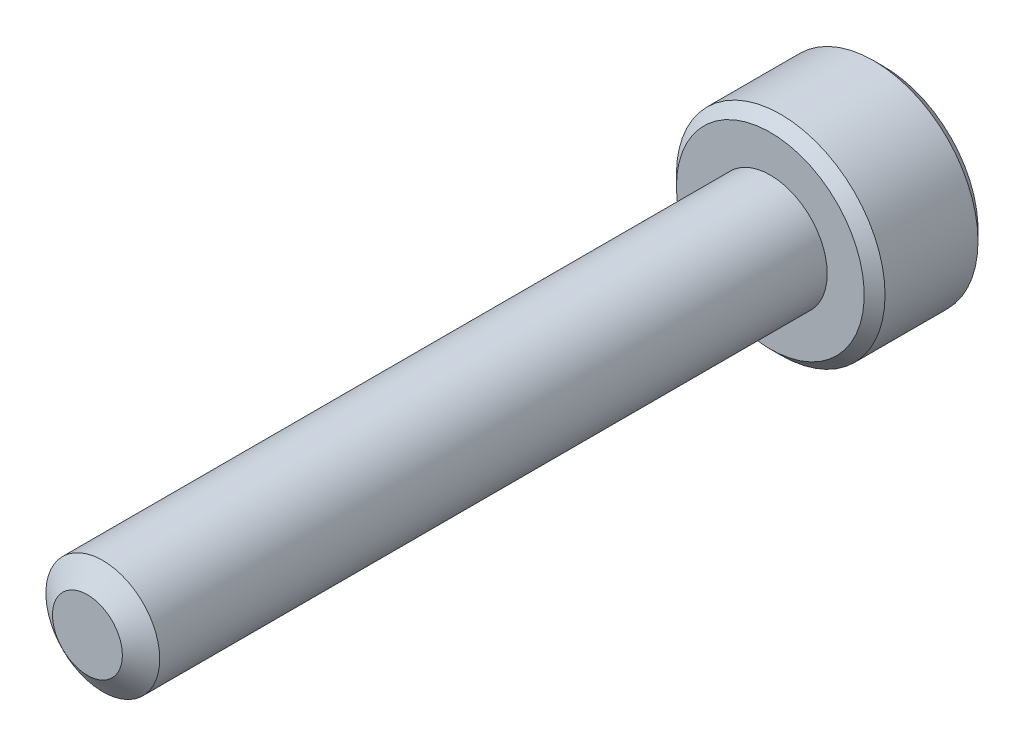
SolidWorks part; units mm, degrees
other "DetailItem1"
material "1.4310 (X10CrNi18-8)"
ref_plane "Front Plane" through (0, 0, 0) normal (0, 0, 1) x (1, 0, 0)
ref_plane "Top Plane" through (0, 0, 0) normal (0, 1, 0) x (1, 0, 0)
ref_plane "Right Plane" through (0, 0, 0) normal (1, 0, 0) x (0, 0, -1)
sketch "Sketch1" plane through (0, 0, 0) normal (0, 0, 1) x (1, 0, 0)
  circle A0 centre (0, 0) radius 1.5
  dimension "OD" = 3
extrude "Extrude1" add sketch "Sketch1" against normal blind 18
sketch "Sketch2" plane through (0, 0, 0) normal (0, 0, 1) x (1, 0, 0)
  circle A0 centre (0, 0) radius 1.5 construction
  circle A1 centre (0, 0) radius 1.5
curve "Helix/Spiral1" pitch 0.5 height 18.5 turns 37 parameters "pitch"=0.5
sketch "Sketch3" plane through (0, 0, 0) normal (1, 0, 0) x (0, 0, -1)
  line L0 (-0.4375, 1.5) -> (-0.25, 1.1752)
  line L1 (-0.25, 1.1752) -> (-0.1875, 1.1752)
  line L2 (-0.1875, 1.1752) -> (0, 1.5)
  line L3 (-0.4375, 1.5) -> (0, 1.5)
  line L4 (-0.2187, 1.5) -> (-0.2188, 1.1752) construction
  line L5 (-0.3438, 1.3376) -> (-0.0938, 1.3376) construction
  line L6 (0, 1.5) -> (0, -1.5) construction
  dimension "D1" = 0.0625
  dimension "D2" = 0.25
  dimension "D3" = 60
sweep "Cut-Sweep1" [suppressed] cut profiles "Sketch3" path "Helix/Spiral1"
sketch "Sketch4" plane through (0, 0, 0) normal (1, 0, 0) x (0, 0, -1)
  line L0 (0.4053, 1.5) -> (0, 0.9212)
  line L1 (0, 0.9212) -> (0, 1.5)
  line L2 (0.4053, 1.5) -> (0, 1.5)
  line L3 (-0.4375, 1.5) -> (0, 1.5) construction
  line L4 (0, 0) -> (7.0209, 0) construction
  dimension "D1" = 55
  dimension "D2" = 0.254
revolve "Cut-Revolve1" cut sketch "Sketch4" angle 360 about L4
sketch "Sketch6" plane through (0, 0, -18) normal (0, 0, -1) x (-1, 0, 0)
  circle A0 centre (0, 0) radius 2.75
  dimension "head dia" = 5.5
extrude "Extrude2" add sketch "Sketch6" along normal blind 3
sketch "Sketch7" plane through (0, 0, -21) normal (0, 0, -1) x (-1, 0, 0)
  line L1 (0, 1.4434) -> (-1.25, 0.7217)
  line L2 (-1.25, 0.7217) -> (-1.25, -0.7217)
  line L3 (-1.25, -0.7217) -> (0, -1.4434)
  line L4 (0, -1.4434) -> (1.25, -0.7217)
  line L5 (1.25, -0.7217) -> (1.25, 0.7217)
  line L6 (1.25, 0.7217) -> (0, 1.4434)
  circle A0 centre (0, 0) radius 1.25 construction
  dimension "hex dia" = 2.5
extrude "Cut-Extrude1" cut sketch "Sketch7" against normal blind 1.875
sketch "Sketch8" plane through (0, 0, -21) normal (0, 0, -1) x (-1, 0, 0)
  circle A0 centre (0, 0) radius 1.4434
extrude "Cut-Extrude2" cut sketch "Sketch8" against normal through all draft 45
chamfer "Chamfer1" distance 0.275 angle 45 2 edges at (-2.75, 0, -21) (-2.75, 0, -18)
sketch "Sketch10" plane through (0, 0, -18) normal (0, 0, 1) x (1, 0, 0)
  circle A1 centre (0, 0) radius 1.5
  circle A2 centre (0, 0) radius 1.5
  dimension "D1" = 0
ref_plane "Plane1" through (0, 0, 0) normal (0, 0, 1) x (1, 0, 0)
extrude "partial thread" [suppressed] add sketch "Sketch10" along normal up to surface (4 mm away) separate body up to plane "Plane1"
chamfer "Chamfer2" [suppressed] distance 0.06 angle 45
combine bodies "Combine1" [suppressed] operation type add bodies to combine 107 108
sketch "Sketch9" plane through (0, 0, 0) normal (1, 0, 0) x (0, 0, -1)
  line L0 (0, 1.5) -> (0, -1.5) construction
  line L1 (1.25, 1.5) -> (1.25, -1.5) construction
  dimension "D1" = 1.25
equation "\"D3@Helix/Spiral1\" = \"screw length@Extrude1\"+\"pitch@Helix/Spiral1\""
equation "\"D1@Sketch3\" = \"pitch@Helix/Spiral1\"*.125"
equation "\"D2@Sketch3\" = \"pitch@Helix/Spiral1\"*.5"
equation "\"D1@Cut-Extrude1\" = \"hex dia@Sketch7\"*.75"
equation "\"D1@Chamfer1\" = \"head dia@Sketch6\"*.05"
equation "\"D1@Sketch9\" = \"pitch@Helix/Spiral1\"*2.5"
equation "\"D1@Chamfer2\"=\"OD@Sketch1\"*.02"
